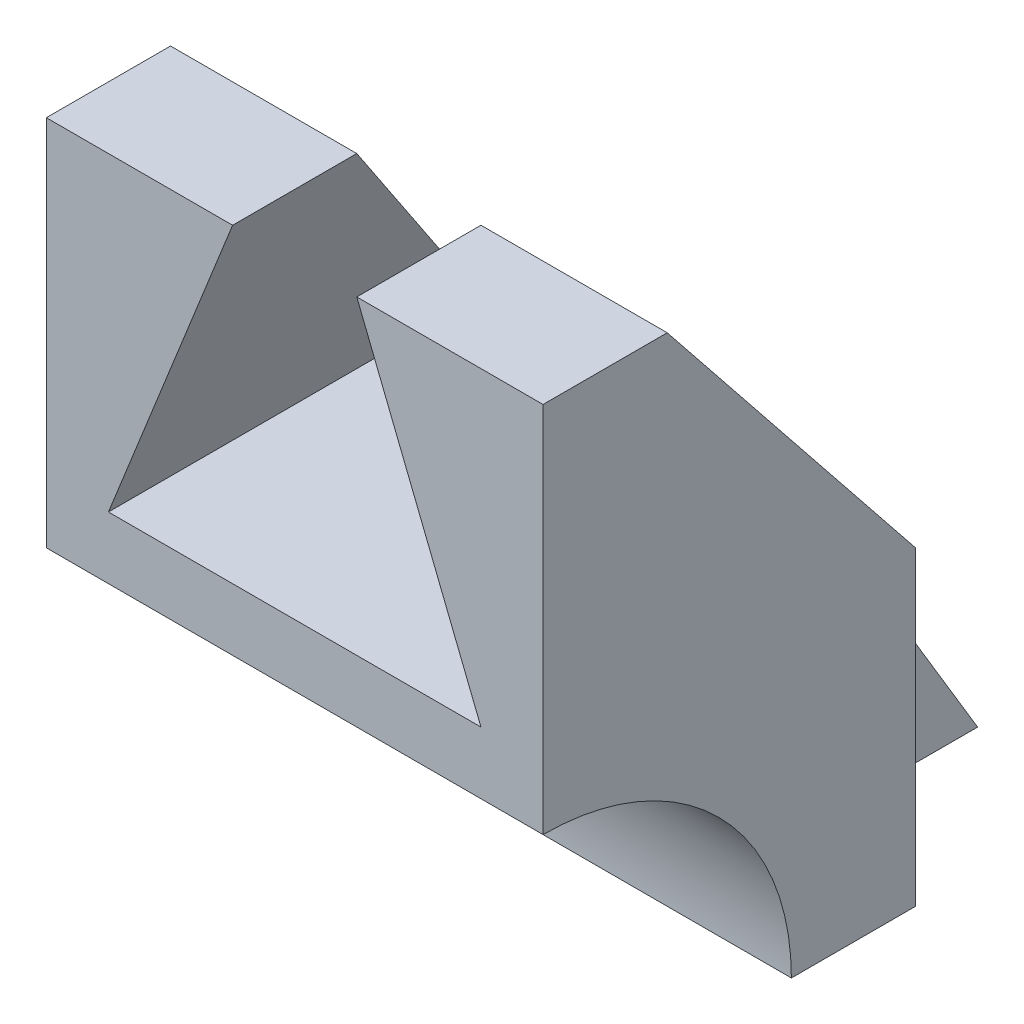
SolidWorks part; units mm, degrees
ref_plane "Front Plane" through (0, 0, 0) normal (0, 0, 1) x (1, 0, 0)
ref_plane "Top Plane" through (0, 0, 0) normal (0, 1, 0) x (1, 0, 0)
ref_plane "Right Plane" through (0, 0, 0) normal (1, 0, 0) x (0, 0, -1)
sketch "Sketch1" plane through (0, 0, 0) normal (1, 0, 0) x (0, 0, -1)
  line L0 (0, 50) -> (10, 50)
  line L1 (20, 0) -> (30, 0)
  line L2 (0, 20) -> (0, 50)
  line L3 (0, 50) -> (10, 50)
  line L4 (30, 0) -> (30, 25)
  line L5 (10, 50) -> (30, 25)
  line L6 (30, 0) -> (45, 0)
  line L7 (45, 0) -> (30, 25)
  arc A0 (20, 0) -> (0, 20) centre (0, 0) ccw
  dimension "D1" = 20
  dimension "D2" = 10
  dimension "D3" = 25
  dimension "D4" = 45
  dimension "D5" = 50
extrude "Boss-Extrude1" add sketch "Sketch1" along normal mid plane 40 contours A0 L1 L4 L5 L0 L2 region at (0, 26.0906, -14.9598)
extrude "Boss-Extrude2" add sketch "Sketch1<3>" along normal mid plane 20 contours L6 L7 L4 region at (0, 8.3333, -35)
sketch "Sketch1<3>" plane through (0, 0, 0) normal (1, 0, 0) x (0, 0, -1) same geometry as "Sketch1"
sketch "Sketch2" plane through (0, 0, 0) normal (0, 0, 1) x (1, 0, 0)
  line L0 (15, 25) -> (5, 50)
  line L1 (20, 50) -> (-20, 50) construction
  line L2 (5, 50) -> (-5, 50)
  line L4 (-15, 25) -> (15, 25)
  line L5 (20, 25) -> (10, 25) construction
  line L6 (-5, 50) -> (-15, 25)
  dimension "D1" = 5
  dimension "D2" = 5
extrude "Cut-Extrude1" cut sketch "Sketch2" against normal through all
